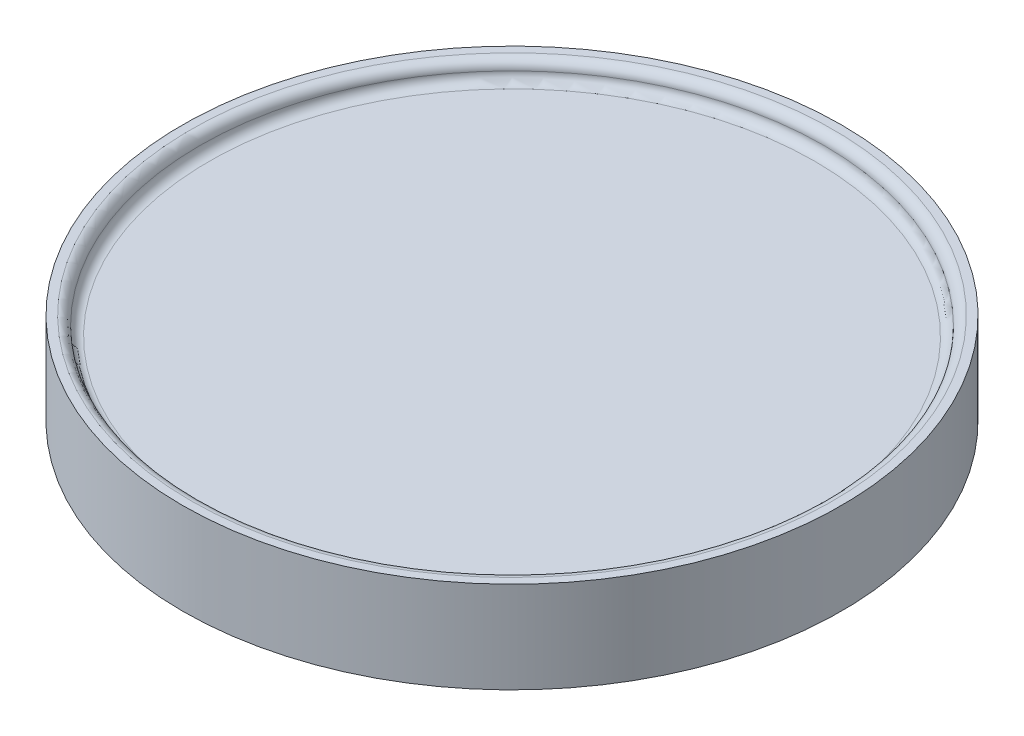
SolidWorks part; units mm, degrees
ref_plane "Front Plane" through (0, 0, 0) normal (0, 0, 1) x (1, 0, 0)
ref_plane "Top Plane" through (0, 0, 0) normal (0, 1, 0) x (1, 0, 0)
ref_plane "Right Plane" through (0, 0, 0) normal (1, 0, 0) x (0, 0, -1)
sketch "Sketch1" plane through (0, 0, 0) normal (0, 1, 0) x (1, 0, 0)
  circle A0 centre (0, 0) radius 457.2
extrude "Boss-Extrude1" add sketch "Sketch1" along normal blind 127
sketch "Sketch2" plane through (0, 127, 0) normal (0, 1, 0) x (1, 0, 0)
  circle A0 centre (0, 0) radius 433.0364
extrude "Cut-Extrude2" cut sketch "Sketch2" against normal blind 25.4 contours A0
fillet "Fillet3" radius 12.7 1 edges at (0, 127, 433.0364)
fillet "Fillet4" radius 12.7 1 edges at (0, 101.6, 433.0364)
